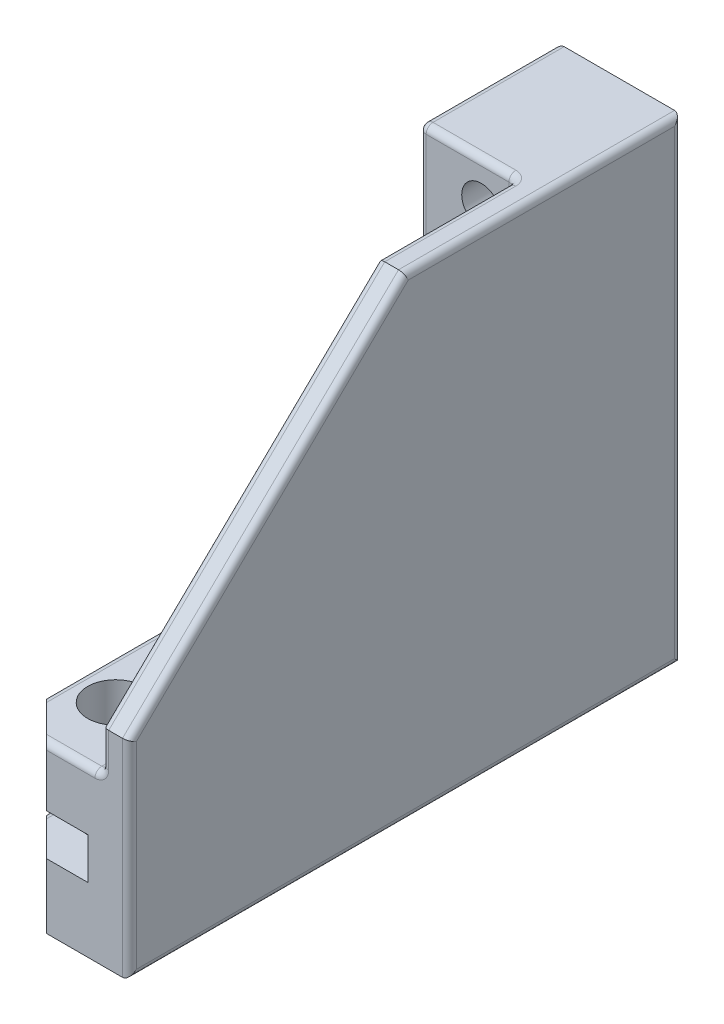
SolidWorks part; units mm, degrees
ref_plane "Front Plane" through (0, 0, 0) normal (0, 0, 1) x (1, 0, 0)
ref_plane "Top Plane" through (0, 0, 0) normal (0, 1, 0) x (1, 0, 0)
ref_plane "Right Plane" through (0, 0, 0) normal (1, 0, 0) x (0, 0, -1)
sketch "Sketch1" plane through (0, 0, 0) normal (0, 0, 1) x (1, 0, 0)
  line L1 (0, 0) -> (9, 0)
  line L2 (0, 0) -> (0, 34.4)
  line L3 (0, 34.4) -> (9, 34.4)
  line L4 (9, 0) -> (9, 34.4)
  circle A0 centre (4.5, 24.4) radius 1.4224
  circle A1 centre (4.5, 15.4) radius 1.4224
  circle A2 centre (4.5, 31.4) radius 1.4224
  dimension "D3" = 2.8448
  dimension "D7" = 2.8448
  dimension "D8" = 7
  dimension "D1" = 9
  dimension "D2" = 34.4
  dimension "D4" = 4.5
  dimension "D5" = 9
  dimension "D6" = 10
extrude "Boss-Extrude1" add sketch "Sketch1" along normal blind 40 contours L1 L4 L3 L2 A1 A0 | A0 | A1 | A2 region at (0.3556, 17.2, 0) region at (4.5, 24.4, 0) region at (4.5, 15.4, 0)
extrude "Cut-Extrude1" cut sketch "Sketch1<3>" along normal blind 10 contours A0 | A2 | A1 region at (4.5, 24.4, 0) region at (4.5, 31.4, 0)
sketch "Sketch1<3>" plane through (0, 0, 0) normal (0, 0, 1) x (1, 0, 0) same geometry as "Sketch1"
sketch "Sketch2" plane through (9, 0, 0) normal (1, 0, 0) x (0, 0, -1)
  line L0 (0, 0) -> (0, 34.4) construction
  line L1 (0, 4.7) -> (-40, 4.7)
  line L2 (0, 4.7) -> (0, 7.7)
  line L3 (0, 7.7) -> (-40, 7.7)
  line L4 (-40, 4.7) -> (-40, 7.7)
  line L5 (-40, 0) -> (-40, 34.4) construction
  line L6 (-40, 0) -> (0, 0) construction
  dimension "D1" = 3
  dimension "D2" = 7.7
extrude "Cut-Extrude2" cut sketch "Sketch2" against normal blind 6
sketch "Sketch3" plane through (9, 0, 0) normal (1, 0, 0) x (0, 0, -1)
  line L0 (-20, 34.4) -> (-40, 15)
  line L1 (-40, 34.4) -> (0, 34.4) construction
  line L2 (-40, 7.7) -> (-40, 34.4) construction
  line L3 (-40, 0) -> (0, 0) construction
  line L4 (0, 0) -> (0, 34.4) construction
  line L5 (-40, 15) -> (-48.3794, 51.9132)
  line L6 (-48.3794, 51.9132) -> (-20, 34.4)
  dimension "D1" = 15
  dimension "D2" = 20
extrude "Cut-Extrude3" cut sketch "Sketch3" against normal up to surface (9 mm away) up to face at (0, 17.2, 20)
sketch "Sketch4" plane through (0, 0, 0) normal (-1, 0, 0) x (0, 0, 1)
  line L0 (15, 34.4) -> (15, 4.4)
  line L1 (20, 34.4) -> (0, 34.4) construction
  line L2 (15, 4.4) -> (-9.525, 4.4)
  line L3 (-9.525, 4.4) -> (-9.525, 34.4)
  line L4 (-9.525, 34.4) -> (15, 34.4)
  line L6 (0, 0) -> (0, 34.4) construction
  line L7 (0, 0) -> (0, 34.4) construction
  dimension "D1" = 30
  dimension "D2" = 15
  dimension "D3" = 9.525
sketch "Sketch5" plane through (9, 0, 0) normal (-1, 0, 0) x (0, 0, 1)
  line L0 (10, 34.4) -> (10, 12)
  line L1 (10, 12) -> (40, 12)
  line L5 (40, 15) -> (20, 34.4)
  line L6 (20, 34.4) -> (0, 34.4)
  line L7 (0, 34.4) -> (0, 0)
  line L8 (0, 0) -> (40, 0)
  line L9 (40, 0) -> (40, 15)
  line L10 (40, 15) -> (20, 34.4)
  line L11 (20, 34.4) -> (0, 34.4)
  line L12 (0, 34.4) -> (0, 0)
  line L13 (0, 0) -> (40, 0)
  line L14 (40, 0) -> (40, 15)
  line M18 (0, 34.4) -> (20, 34.4)
  line M19 (20, 34.4) -> (40, 15)
  line M20 (40, 15) -> (40, 7.7)
  dimension "D2" = 10
  dimension "D3" = 12
  dimension "D1" = 0
extrude "Cut-Extrude6" cut sketch "Sketch5" along normal blind 7 contours L1 L0 M18 M19 M20 region at (9, 21.2789, 21.6179)
sketch "Sketch6" plane through (0, 0, 0) normal (0, -1, 0) x (1, 0, 0)
  line L0 (0, 40) -> (9, 40) construction
  line L1 (9, 40) -> (9, 0) construction
  circle A0 centre (6, 35) radius 2.0193
  circle A1 centre (6, 20) radius 2.0193
  dimension "D1" = 4.0386
  dimension "D4" = 3
  dimension "D2" = 15
  dimension "D3" = 5
extrude "Cut-Extrude5" cut sketch "Sketch6" against normal blind 20
fillet "Fillet2" radius 0.5 5 edges at (0, 34.4, 10) (0, 24.7, 30) (0, 7.5, 40) (0, 0, 20) (0, 17.2, 0)
chamfer "Chamfer4" distance 3 angle 45 2 edges at (9, 2.35, 40) (9, 9.85, 40)
mirror "Mirror1" about plane through (9, 0, 40) normal (-1, 0, 0) of bodies 107
sketch "Sketch7" plane through (0, 0, 0) normal (-1, 0, 0) x (0, 0, 1)
  line L1 (67.0613, -21.0896) -> (-7.2489, -21.0896)
  line L2 (67.0613, -21.0896) -> (67.0613, 74.0764)
  line L3 (67.0613, 74.0764) -> (-7.2489, 74.0764)
  line L4 (-7.2489, -21.0896) -> (-7.2489, 74.0764)
extrude "Cut-Extrude7" cut sketch "Sketch7" against normal blind 9
fillet "Fillet3" radius 0.5 15 edges at (9, 2.35, 0) (9, 4.7, 18.5) (9, 2.35, 37) (9, 0, 18.5) (9, 23.2, 10) (9, 12, 23.5) (9, 9.85, 37) (9, 7.7, 18.5) (9, 21.05, 0) (9, 34.4, 5) (16, 23.2, 10) (16, 34.4, 15) (16, 24.7, 30) (16, 13.5, 40) (16, 12, 25)
